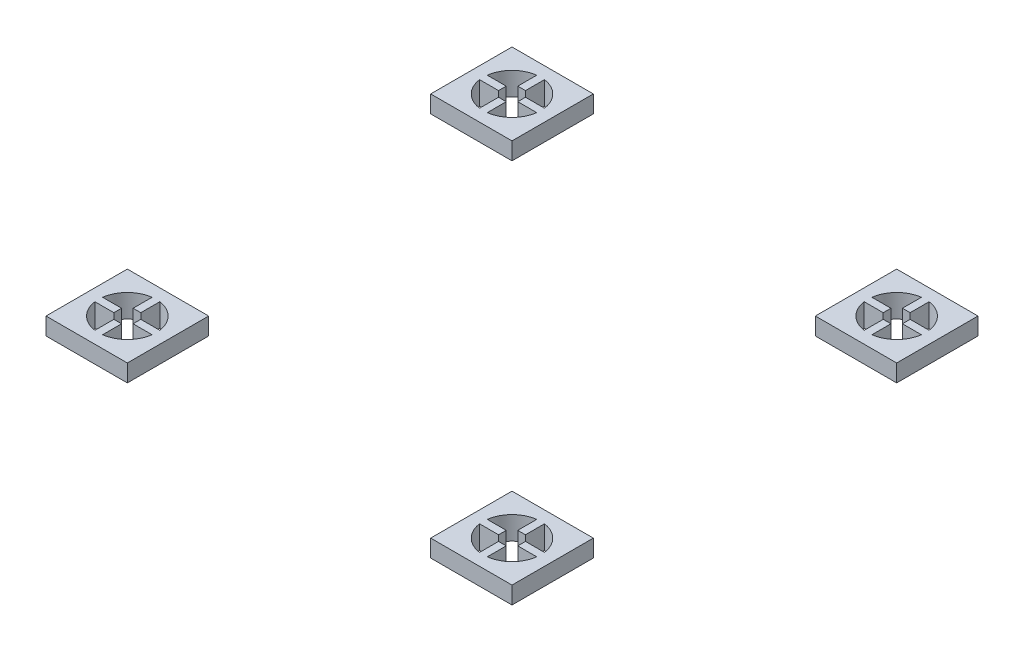
SolidWorks part; units mm, degrees
ref_plane "Front Plane" through (0, 0, 0) normal (0, 0, 1) x (1, 0, 0)
ref_plane "Top Plane" through (0, 0, 0) normal (0, 1, 0) x (1, 0, 0)
ref_plane "Right Plane" through (0, 0, 0) normal (1, 0, 0) x (0, 0, -1)
sketch "Sketch2" plane through (0, 0, 0) normal (0, 1, 0) x (1, 0, 0)
  line L0 (490, -425.6697) -> (490, -475)
  line L1 (490, -475) -> (510, -475)
  line L2 (-510, -425.6697) -> (-510, -475)
  line L3 (510, -425.6697) -> (510, -475)
  line L4 (574.3303, -510) -> (525, -510)
  line L5 (574.3303, -490) -> (525, -490)
  line L6 (525, -490) -> (525, -510)
  line L7 (490, -574.3303) -> (490, -525)
  line L8 (510, -574.3303) -> (510, -525)
  line L9 (510, -525) -> (490, -525)
  line L10 (425.6697, -490) -> (475, -490)
  line L11 (425.6697, -510) -> (475, -510)
  line L12 (475, -510) -> (475, -490)
  line L13 (500, -425) -> (500, -475) construction
  line L14 (490, 574.3303) -> (490, 525)
  line L15 (490, 525) -> (510, 525)
  line L16 (510, 574.3303) -> (510, 525)
  line L17 (574.3303, 490) -> (525, 490)
  line L18 (574.3303, 510) -> (525, 510)
  line L19 (525, 510) -> (525, 490)
  line L20 (490, 425.6697) -> (490, 475)
  line L21 (510, 425.6697) -> (510, 475)
  line L22 (510, 475) -> (490, 475)
  line L23 (425.6697, 510) -> (475, 510)
  line L24 (425.6697, 490) -> (475, 490)
  line L25 (475, 490) -> (475, 510)
  line L26 (500, 575) -> (500, 525) construction
  line L27 (-510, -475) -> (-490, -475)
  line L28 (-490, -425.6697) -> (-490, -475)
  line L29 (-425.6697, -510) -> (-475, -510)
  line L30 (-425.6697, -490) -> (-475, -490)
  line L31 (-475, -490) -> (-475, -510)
  line L32 (-510, -574.3303) -> (-510, -525)
  line L33 (-490, -574.3303) -> (-490, -525)
  line L34 (-490, -525) -> (-510, -525)
  line L35 (-574.3303, -490) -> (-525, -490)
  line L36 (-574.3303, -510) -> (-525, -510)
  line L37 (-525, -510) -> (-525, -490)
  line L38 (-510, 574.3303) -> (-510, 525)
  line L39 (-510, 525) -> (-490, 525)
  line L40 (-490, 574.3303) -> (-490, 525)
  line L41 (-425.6697, 490) -> (-475, 490)
  line L42 (-425.6697, 510) -> (-475, 510)
  line L43 (-475, 510) -> (-475, 490)
  line L44 (-510, 425.6697) -> (-510, 475)
  line L45 (-490, 425.6697) -> (-490, 475)
  line L46 (-490, 475) -> (-510, 475)
  line L47 (-574.3303, 510) -> (-525, 510)
  line L48 (-574.3303, 490) -> (-525, 490)
  line L49 (-525, 490) -> (-525, 510)
  line L50 (-500, -425) -> (-500, -475) construction
  line L51 (-500, 575) -> (-500, 525) construction
  line L52 (-605.7125, 605.7125) -> (-394.2875, 605.7125)
  line L53 (-605.7125, 605.7125) -> (-605.7125, 394.2875)
  line L54 (-605.7125, 394.2875) -> (-394.2875, 394.2875)
  line L55 (-394.2875, 605.7125) -> (-394.2875, 394.2875)
  line L56 (-605.7125, 605.7125) -> (-394.2875, 394.2875) construction
  line L57 (-605.7125, 394.2875) -> (-394.2875, 605.7125) construction
  line L58 (-605.7125, -394.2875) -> (-394.2875, -394.2875)
  line L59 (-605.7125, -394.2875) -> (-605.7125, -605.7125)
  line L60 (-605.7125, -605.7125) -> (-394.2875, -605.7125)
  line L61 (-394.2875, -394.2875) -> (-394.2875, -605.7125)
  line L62 (-605.7125, -394.2875) -> (-394.2875, -605.7125) construction
  line L63 (-605.7125, -605.7125) -> (-394.2875, -394.2875) construction
  line L64 (605.7125, 605.7125) -> (394.2875, 605.7125)
  line L65 (605.7125, 605.7125) -> (605.7125, 394.2875)
  line L66 (605.7125, 394.2875) -> (394.2875, 394.2875)
  line L67 (394.2875, 605.7125) -> (394.2875, 394.2875)
  line L68 (605.7125, 605.7125) -> (394.2875, 394.2875) construction
  line L69 (605.7125, 394.2875) -> (394.2875, 605.7125) construction
  line L70 (605.7125, -394.2875) -> (394.2875, -394.2875)
  line L71 (605.7125, -394.2875) -> (605.7125, -605.7125)
  line L72 (605.7125, -605.7125) -> (394.2875, -605.7125)
  line L73 (394.2875, -394.2875) -> (394.2875, -605.7125)
  line L74 (605.7125, -394.2875) -> (394.2875, -605.7125) construction
  line L75 (605.7125, -605.7125) -> (394.2875, -394.2875) construction
  arc A0 (490, -425.6697) -> (425.6697, -490) centre (500, -500) ccw
  arc A1 (425.6697, -510) -> (490, -574.3303) centre (500, -500) ccw
  arc A2 (510, -574.3303) -> (574.3303, -510) centre (500, -500) ccw
  arc A3 (574.3303, -490) -> (510, -425.6697) centre (500, -500) ccw
  arc A4 (490, -425.6697) -> (529.2889, -430.9554) centre (500, -500) cw
  arc A5 (490, 574.3303) -> (425.6697, 510) centre (500, 500) ccw
  arc A6 (425.6697, 490) -> (490, 425.6697) centre (500, 500) ccw
  arc A7 (510, 425.6697) -> (574.3303, 490) centre (500, 500) ccw
  arc A8 (574.3303, 510) -> (510, 574.3303) centre (500, 500) ccw
  arc A9 (490, 574.3303) -> (529.2889, 569.0446) centre (500, 500) cw
  arc A10 (-510, -425.6697) -> (-574.3303, -490) centre (-500, -500) ccw
  arc A11 (-574.3303, -510) -> (-510, -574.3303) centre (-500, -500) ccw
  arc A12 (-490, -574.3303) -> (-425.6697, -510) centre (-500, -500) ccw
  arc A13 (-425.6697, -490) -> (-490, -425.6697) centre (-500, -500) ccw
  arc A14 (-510, -425.6697) -> (-470.7111, -430.9554) centre (-500, -500) cw
  arc A15 (-510, 574.3303) -> (-574.3303, 510) centre (-500, 500) ccw
  arc A16 (-574.3303, 490) -> (-510, 425.6697) centre (-500, 500) ccw
  arc A17 (-490, 425.6697) -> (-425.6697, 490) centre (-500, 500) ccw
  arc A18 (-425.6697, 510) -> (-490, 574.3303) centre (-500, 500) ccw
  arc A19 (-510, 574.3303) -> (-470.7111, 569.0446) centre (-500, 500) cw
  point P22 (-500, -500)
  point P24 (-500, -500)
  point P48 (500, -500)
  point P49 (500, -500)
  point P71 (500, 500)
  point P72 (500, 500)
  point P87 (-500, 500)
  point P88 (-500, 500)
  point P104 (0, 0)
extrude "Boss-Extrude1" add sketch "Sketch2" along normal blind 60 contours L55 L52 L53 L54 A15 A19 A18 L42 L43 L41 A17 L45 L46 L44 A16 L48 L49 L47 | L64 L67 L66 L65 A5 A9 A8 L18 L19 L17 A7 L21 L22 L20 A6 L24 L25 L23 | L70 L73 L72 L71 A0 A4 A3 L5 L6 L4 A2 L8 L9 L7 A1 L11 L12 L10 | L61 L58 L59 L60 A10 A14 A13 L30 L31 L29 A12 L33 L34 L32 A11 L36 L37 L35 | A14 L2 L27 L28 | A4 L0 L1 L3 | A9 L14 L15 L16 | A19 L38 L39 L40 region at (500, 0, 450.111) region at (-500, 0, 450.111) region at (500, 0, -549.889) region at (-500, 0, -549.889) region at (-500, 0, -602.7225) region at (-500, 0, 397.2775) region at (602.7225, 0, -500) region at (602.7225, 0, 500)
chamfer "Chamfer1" distance 15 angle 45 4 edges at (-500, 0, -605.7125) (-394.2875, 0, -500) (-500, 0, -394.2875) (-605.7125, 0, -500)
chamfer "Chamfer2" distance 15 angle 45 4 edges at (605.7125, 0, -500) (500, 0, -394.2875) (394.2875, 0, -500) (500, 0, -605.7125)
chamfer "Chamfer3" distance 15 angle 45 4 edges at (605.7125, 0, 500) (500, 0, 605.7125) (394.2875, 0, 500) (500, 0, 394.2875)
chamfer "Chamfer4" distance 15 angle 45 4 edges at (-605.7125, 0, 500) (-500, 0, 605.7125) (-394.2875, 0, 500) (-500, 0, 394.2875)
